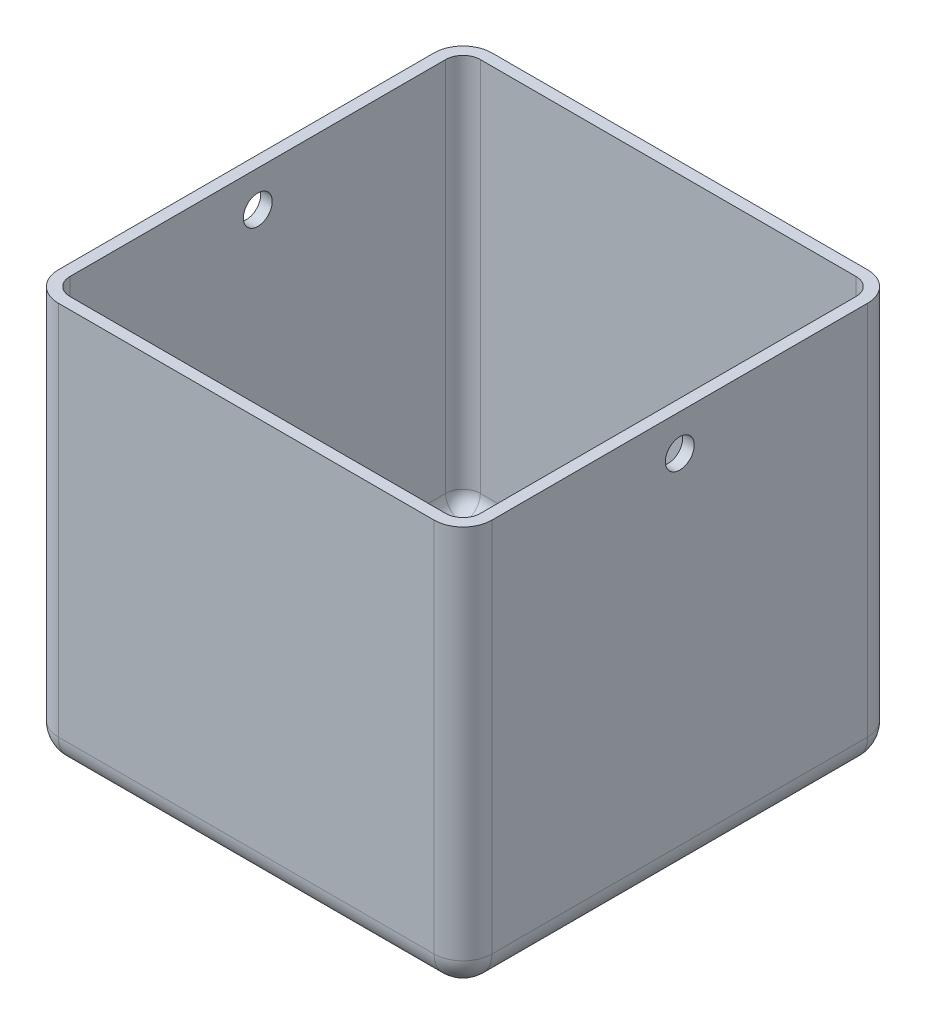
SolidWorks part; units mm, degrees
ref_plane "Front Plane" through (0, 0, 0) normal (0, 0, 1) x (1, 0, 0)
ref_plane "Top Plane" through (0, 0, 0) normal (0, 1, 0) x (1, 0, 0)
ref_plane "Right Plane" through (0, 0, 0) normal (1, 0, 0) x (0, 0, -1)
sketch "Sketch1" plane through (0, 0, 0) normal (0, 1, 0) x (1, 0, 0)
  line L1 (-30, -30) -> (30, -30)
  line L2 (-30, -30) -> (-30, 30)
  line L3 (-30, 30) -> (30, 30)
  line L4 (30, -30) -> (30, 30)
  line L5 (-30, -30) -> (30, 30) construction
  line L6 (-30, 30) -> (30, -30) construction
  point P0 (0, 0)
  dimension "D1" = 60
  dimension "D2" = 60
extrude "Boss-Extrude1" add sketch "Sketch1" along normal blind 56
fillet "Fillet1" radius 4 8 edges at (-30, 0, 0) (0, 0, -30) (30, 0, 0) (0, 0, 30) (-30, 28, -30) (-30, 28, 30) (30, 28, -30) (30, 28, 30)
shell "Shell1" thickness 1.6 removed face at (0, 56, 0)
sketch "Sketch2" plane through (0, 1.6, 0) normal (0, 1, 0) x (1, 0, 0)
  line L28 (18.8649, 1.6027) -> (12.7611, 8.2248)
  line L29 (8.3493, 10.1583) -> (-8.2959, 10.1583)
  line L30 (-12.7077, 8.2248) -> (-18.8115, 1.6027)
  line L31 (-12.7077, -8.4082) -> (-18.8115, -1.7861)
  line L32 (8.3493, -10.3417) -> (-8.2959, -10.3417)
  line L33 (18.8649, -1.7861) -> (12.7611, -8.4082)
  line L34 (20.3355, 2.9582) -> (14.2317, 9.5803)
  line L35 (8.3493, 12.1583) -> (-8.2959, 12.1583)
  line L36 (-14.1783, 9.5803) -> (-20.2821, 2.9582)
  line L37 (-14.1783, -9.7637) -> (-20.2821, -3.1416)
  line L38 (8.3493, -12.3417) -> (-8.2959, -12.3417)
  line L39 (20.3355, -3.1416) -> (14.2317, -9.7637)
  arc A20 (12.7611, 8.2248) -> (8.3493, 10.1583) centre (8.3493, 4.1583) ccw
  arc A21 (-8.2959, 10.1583) -> (-12.7077, 8.2248) centre (-8.2959, 4.1583) ccw
  arc A22 (-18.8115, 1.6027) -> (-18.8115, -1.7861) centre (-16.9733, -0.0917) ccw
  arc A23 (-8.2959, -10.3417) -> (-12.7077, -8.4082) centre (-8.2959, -4.3417) cw
  arc A24 (12.7611, -8.4082) -> (8.3493, -10.3417) centre (8.3493, -4.3417) cw
  arc A25 (18.8649, 1.6027) -> (18.8649, -1.7861) centre (17.0267, -0.0917) cw
  arc A26 (14.2317, 9.5803) -> (8.3493, 12.1583) centre (8.3493, 4.1583) ccw
  arc A27 (-8.2959, 12.1583) -> (-14.1783, 9.5803) centre (-8.2959, 4.1583) ccw
  arc A28 (-20.2821, 2.9582) -> (-20.2821, -3.1416) centre (-16.9733, -0.0917) ccw
  arc A29 (-8.2959, -12.3417) -> (-14.1783, -9.7637) centre (-8.2959, -4.3417) cw
  arc A30 (14.2317, -9.7637) -> (8.3493, -12.3417) centre (8.3493, -4.3417) cw
  arc A31 (20.3355, 2.9582) -> (20.3355, -3.1416) centre (17.0267, -0.0917) cw
  dimension "D1" = 2
extrude "Cut-Extrude1" cut sketch "Sketch2" against normal through all contours L28 A20 L29 A21 L30 A22 L31 A23 L32 A24 L33 A25
extrude "Boss-Extrude2" add sketch "Sketch2<4>" along normal blind 8
sketch "Sketch2<4>" plane through (0, 1.6, 0) normal (0, 1, 0) x (1, 0, 0) same geometry as "Sketch2"
sketch "Sketch3" plane through (0, 0, -12.1583) normal (0, 0, -1) x (-1, 0, 0)
  line L0 (-0.0267, 9.6) -> (-0.0267, 1.6) construction
  line L1 (-8.3493, 9.6) -> (8.2959, 9.6) construction
  circle A0 centre (-0.0267, 5.6) radius 2.4
extrude "Cut-Extrude2" cut sketch "Sketch3" against normal up to surface (24.5 mm away) up to face at (0.0267, 5.6, 12.3417)
sketch "Sketch4" plane through (30, 0, 0) normal (1, 0, 0) x (0, 0, -1)
  line L0 (0, 56) -> (0, 46)
  line L1 (0, 55.3) -> (-3.7239, 53.15)
  line L2 (-3.7239, 53.15) -> (-3.7239, 48.85)
  line L3 (-3.7239, 48.85) -> (0, 46.7)
  line L4 (0, 46.7) -> (3.7239, 48.85)
  line L5 (3.7239, 48.85) -> (3.7239, 53.15)
  line L6 (3.7239, 53.15) -> (0, 55.3)
  line L7 (26, 56) -> (-26, 56)
  line L8 (0, 56) -> (0, 62.3252)
  circle A0 centre (0, 51) radius 4.3 construction
  circle A1 centre (0, 51) radius 2
extrude "Cut-Extrude3" cut sketch "Sketch4" against normal up to surface (60 mm away) contours L0 A1 | L0 A1 region at (30, 51, -0.8488) region at (30, 51, 0.8488) up to face at (-30, 30, 0)
